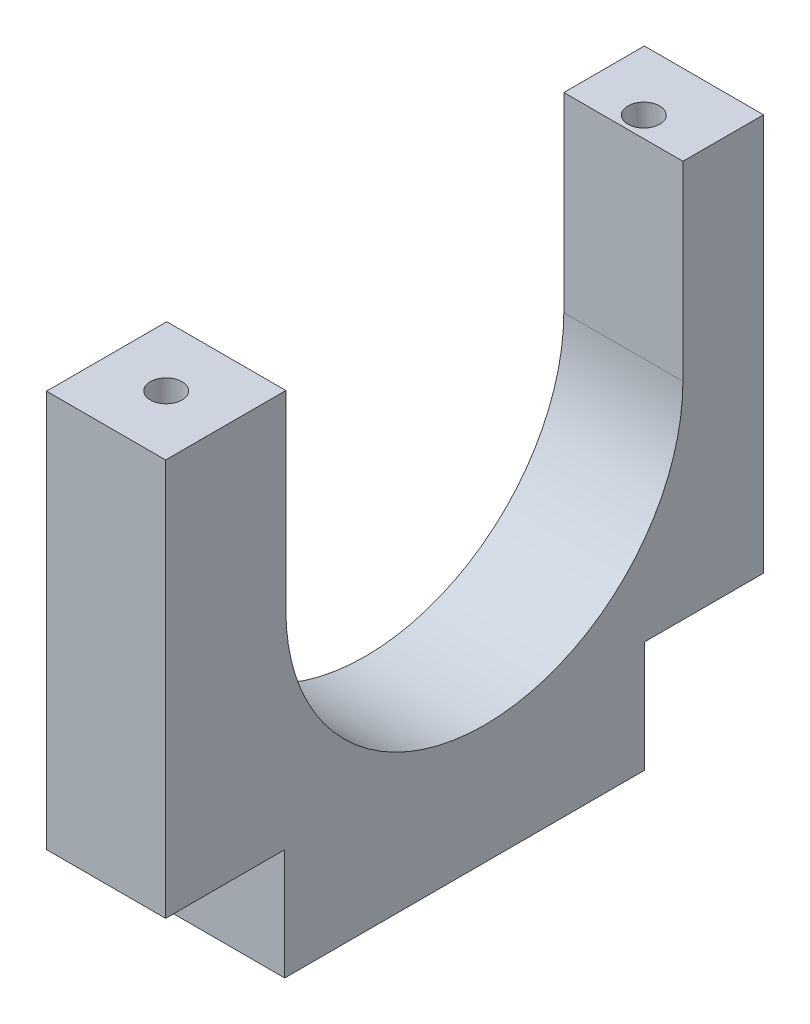
SolidWorks part; units mm, degrees
ref_plane "Front Plane" through (0, 0, 0) normal (0, 0, 1) x (1, 0, 0)
ref_plane "Top Plane" through (0, 0, 0) normal (0, 1, 0) x (1, 0, 0)
ref_plane "Right Plane" through (0, 0, 0) normal (1, 0, 0) x (0, 0, -1)
sketch "Sketch1" plane through (0, 0, 0) normal (0, 1, 0) x (1, 0, 0)
  line L0 (-58, -56) -> (58, -56)
  line L1 (-58, -56) -> (-58, 56)
  line L2 (58, -56) -> (58, 56)
  line L3 (-58, 56) -> (58, 56)
  line L4 (-58, -56) -> (58, 56) construction
  line L5 (58, -56) -> (-58, 56) construction
  line L6 (-63, -61) -> (-63, 61)
  line L7 (-63, 61) -> (63, 61)
  line L8 (63, -61) -> (63, 61)
  line L9 (-63, -61) -> (63, -61)
  point P1 (0, 0)
  dimension "D1" = 116
  dimension "D2" = 112
  dimension "D3" = 5
extrude "Boss-Extrude1" add sketch "Sketch1" along normal blind 15
fillet "Fillet1" radius 10 1 edges at (58, 7.5, -56)
fillet "Fillet2" radius 10 1 edges at (-58, 7.5, -56)
fillet "Fillet3" radius 10 1 edges at (-58, 7.5, 56)
fillet "Fillet4" radius 10 1 edges at (58, 7.5, 56)
sketch "Sketch4" plane through (0, 15, 0) normal (0, 1, 0) x (1, 0, 0)
  line L0 (-63, 61) -> (-63, 62.625)
  line L1 (-63, 62.625) -> (-61.675, 62.625)
  line L2 (-61.675, 62.625) -> (-61.675, 80.1975)
  line L3 (-61.675, 80.1975) -> (-57.925, 80.1975)
  line L4 (-65.425, 45.0525) -> (-65.425, 80.1975)
  line L5 (-65.425, 45.0525) -> (-57.925, 45.0525)
  line L6 (-65.425, 80.1975) -> (-57.925, 80.1975)
  line L7 (-57.925, 45.0525) -> (-57.925, 80.1975)
  line L8 (-65.425, 45.0525) -> (-57.925, 80.1975) construction
  line L9 (-65.425, 80.1975) -> (-57.925, 45.0525) construction
  dimension "D1" = 1.625
  dimension "D2" = 1.325
  dimension "D3" = 3.75
extrude "Boss-Extrude3" add sketch "Sketch4" along normal blind 49.75 and the other way up to surface contours L6 L4 L5 L7
sketch "Sketch5" plane through (-57.925, 0, 0) normal (1, 0, 0) x (0, 0, -1)
  line L0 (45.0525, 64.75) -> (80.1975, 64.75) construction
  circle A0 centre (62.625, 64.75) radius 12.5
  dimension "D1" = 25
extrude "Cut-Extrude1" cut sketch "Sketch5" against normal through all
ref_plane "Plane1" through (-61.675, 0, 0) normal (1, 0, 0) x (0, 0, -1)
sketch "Sketch6" plane through (-57.925, 0, 0) normal (1, 0, 0) x (0, 0, -1)
  line L0 (45.0525, 64.75) -> (50.125, 64.75)
  line L1 (45.0525, 64.75) -> (45.0525, 57.25)
  line L2 (45.0525, 0) -> (45.0525, 64.75) construction
  line L3 (45.0525, 57.25) -> (52.625, 57.25)
  arc A0 (50.125, 64.75) -> (75.125, 64.75) centre (62.625, 64.75) ccw construction
  arc A1 (52.625, 57.25) -> (50.125, 64.75) centre (62.625, 64.75) cw
  dimension "D1" = 7.5
extrude "Boss-Extrude4" add sketch "Sketch6" along normal blind 5
sketch "Sketch9" plane through (0, 64.75, 0) normal (0, 1, 0) x (1, 0, 0)
  line L0 (-52.925, 47.5887) -> (-55.425, 47.5887)
  line L1 (-52.925, 50.125) -> (-52.925, 45.0525) construction
  circle A0 centre (-55.425, 47.5887) radius 1.25
  dimension "D2" = 2.5
  dimension "D1" = 2.5
extrude "Cut-Extrude3" cut sketch "Sketch9" against normal through all
mirror "Mirror1" about plane through (-61.675, 0, 0) normal (1, 0, 0) of "Cut-Extrude3", "Boss-Extrude4"
ref_plane "Plane2" through (0, 0, -62.625) normal (0, 0, -1) x (-1, 0, 0)
mirror "Mirror2" about plane through (0, 0, -62.625) normal (0, 0, -1) of "Mirror1", "Boss-Extrude4", "Cut-Extrude3"
fillet "Fillet6" radius 17.5 1 edges at (-57.925, 7.5, -61)
fillet "Fillet7" radius 17.5 3 edges at (-52.7994, 15, -66.1256) (-54.6248, 15, -53.4908) (-57.925, 15, -62.8612)
fillet "Fillet8" radius 2 1 edges at (-63, 7.5, -45.0525)
fillet "Fillet9" radius 17.5 2 edges at (-63.5858, 15, -44.4667) (-61.5, 15, -45.0525)
fillet "Fillet10" radius 17.5 2 edges at (-57.925, 0, -79.3488) (-61.675, 0, -80.1975)
mirror "Mirror4" about plane through (0, 0, 0) normal (0, 0, 1) of "Mirror2", "Mirror1", "Cut-Extrude3", "Boss-Extrude4", "Cut-Extrude1", "Boss-Extrude3"
fillet "Fillet11" radius 2 1 edges at (-63, 7.5, 45.0525)
fillet "Fillet12" radius 17.5 2 edges at (-61.5, 15, 45.0525) (-63.5858, 15, 44.4667)
fillet "Fillet13" radius 17.5 1 edges at (-57.925, 7.5, 61)
fillet "Fillet14" radius 17.5 3 edges at (-54.6248, 15, 53.4908) (-57.925, 15, 62.8612) (-52.7994, 15, 66.1256)
fillet "Fillet15" radius 17.5 2 edges at (-57.925, 0, 79.3488) (-61.675, 0, 80.1975)
mirror "Mirror6" about plane through (0, 0, 0) normal (1, 0, 0) of "Mirror4", "Boss-Extrude3", "Boss-Extrude4", "Cut-Extrude3", "Mirror1", "Mirror2"
fillet "Fillet16" radius 2 1 edges at (63, 7.5, 45.0525)
fillet "Fillet17" radius 17.5 2 edges at (61.5, 15, 45.0525) (63.5858, 15, 44.4667)
fillet "Fillet18" radius 2 1 edges at (63, 7.5, -45.0525)
fillet "Fillet19" radius 17.5 2 edges at (61.5, 15, -45.0525) (63.5858, 15, -44.4667)
fillet "Fillet20" radius 17.5 1 edges at (57.925, 7.5, -61)
fillet "Fillet21" radius 17.5 3 edges at (54.6248, 15, -53.4908) (57.925, 15, -62.8612) (52.7994, 15, -66.1256)
fillet "Fillet22" radius 17.5 1 edges at (57.925, 7.5, 61)
fillet "Fillet23" radius 17.5 3 edges at (57.925, 15, 62.8612) (54.6248, 15, 53.4908) (52.7994, 15, 66.1256)
fillet "Fillet24" radius 17.5 2 edges at (57.925, 0, 79.3488) (61.675, 0, 80.1975)
fillet "Fillet25" radius 17.5 2 edges at (57.925, 0, -79.3488) (61.675, 0, -80.1975)
sketch "Sketch11" plane through (0, 0, 0) normal (0, -1, 0) x (-1, 0, 0)
  line L0 (0, 0) -> (0, 45.4)
  line L1 (0, 45.4) -> (-47.5, 45.4)
  line L3 (-8.25, 0) -> (8.25, 0) construction
  line L4 (0, 8.25) -> (0, -8.25) construction
  line L5 (-47.5, 45.4) -> (47.5, -45.4)
  line L6 (47.5, -45.4) -> (41.3679, -51.8158)
  line L7 (41.3679, -51.8158) -> (-58, 43.159)
  line L8 (-58, -45.0525) -> (-58, 45.0525) construction
  line L9 (41.3679, -51.8158) -> (45.5521, -56)
  line L10 (48, -56) -> (-48, -56) construction
  line L11 (47.5, -45.4) -> (53.7756, -39.1244)
  line L12 (-47.5, 45.4) -> (-41.2244, 51.6756)
  line L13 (-41.2244, 51.6756) -> (53.7756, -39.1244)
  line L14 (53.7756, -39.1244) -> (58, -43.1622)
  line L15 (58, 45.0525) -> (58, -45.0525) construction
  line L16 (-41.2244, 51.6756) -> (-45.7489, 56)
  line L17 (-48, 56) -> (48, 56) construction
  circle A0 centre (-47.5, 45.4) radius 5.875
  circle A1 centre (-47.5, 45.4) radius 8.875
  circle A4 centre (-47.5, -45.4) radius 8.875
  circle A5 centre (-47.5, -45.4) radius 5.875
  circle A6 centre (47.5, 45.4) radius 8.875
  circle A7 centre (47.5, 45.4) radius 5.875
  circle A8 centre (47.5, -45.4) radius 8.875
  circle A9 centre (47.5, -45.4) radius 5.875
  arc A10 (-58, 43.159) -> (-45.7489, 56) centre (-47.5646, 45.4677) cw
  arc A11 (45.5521, -56) -> (58, -43.1622) centre (48.4327, -46.3393) ccw
  line M27 (-58, -45.0525) -> (-58, 45.0525)
  line M28 (-58, 45.0525) -> (-57.925, 45.0525)
  line M29 (-57.925, 45.0525) -> (-57.925, 47.2224)
  arc M30 (-57.925, 47.2224) -> (-48, 56) centre (-48, 46) cw
  line M31 (-48, 56) -> (48, 56)
  line M35 (58, 45.0525) -> (58, -45.0525)
  line M36 (58, -45.0525) -> (57.925, -45.0525)
  line M37 (57.925, -45.0525) -> (57.925, -47.2224)
  arc M38 (57.925, -47.2224) -> (48, -56) centre (48, -46) cw
  line M39 (48, -56) -> (-48, -56)
  dimension "D3" = 11.75
  dimension "D4" = 17.75
  dimension "D1" = 45.4
  dimension "D2" = 47.5
extrude "Boss-Extrude5" add sketch "Sketch11" against normal blind 3.5 contours A8 L9 L14 M39 M38 M37 M36 M35 | A9 L6 A8 L11 | A9 L5 A8 L6 | A9 L11 L13 A8 L5 | A8 L5 A1 L7 | A8 L13 L0 L5 | A1 L5 L0 L13 L1 | A1 L1 L13 | L5 A1 L1 A0 | L1 A1 L12 A0 | A1 L5 A0 L12 L16 | A1 L16 L7 M31 M30 M29 M28 M27
mirror "Mirror7" about plane through (0, 0, 0) normal (0, 0, 1) of "Boss-Extrude5"
sketch "Sketch12" plane through (0, 0, 0) normal (0, -1, 0) x (-1, 0, 0)
  line L0 (0, 0) -> (-4, 0)
  line L1 (0, 0) -> (-0.0984, 56)
  line L2 (-45.7489, 56) -> (45.5521, 56) construction
  line L3 (4, -56.5079) -> (-4, -56.5079)
  line L4 (4, -56.5079) -> (4, 56.5079)
  line L5 (-4, -56.5079) -> (-4, 56.5079)
  line L6 (4, 56.5079) -> (-4, 56.5079)
  line L7 (4, -56.5079) -> (-4, 56.5079) construction
  line L8 (-4, -56.5079) -> (4, 56.5079) construction
  line M6 (-45.7489, -56) -> (-0.0016, -12.2753)
  line M7 (-0.0016, -12.2753) -> (41.3679, -51.8158)
  line M9 (45.5521, -56) -> (-45.7489, -56)
  line M13 (41.3679, 51.8158) -> (-0.0016, 12.2753)
  line M14 (-0.0016, 12.2753) -> (-45.7489, 56)
  line M15 (-45.7489, 56) -> (45.5521, 56)
  dimension "D1" = 4
extrude "Boss-Extrude6" add sketch "Sketch12" against normal up to surface (3.5 mm away) contours L4 L1 M13 M15 M14 | L5 L1 M14 M15 | L5 L4 M9 M7 M6 up to face at (47.5, 3.5, -51.275)
sketch "Sketch13" plane through (0, 0, 0) normal (0, -1, 0) x (-1, 0, 0)
  line L0 (0, 0) -> (0, 42.5)
  circle A0 centre (0, 42.5) radius 1.5
  dimension "D2" = 3
  dimension "D1" = 42.5
extrude "Cut-Extrude4" cut sketch "Sketch13" against normal through all
mirror "Mirror8" about plane through (0, 0, 0) normal (0, 0, 1) of "Cut-Extrude4"
ref_plane "Plane3" through (0, 44.75, 0) normal (0, 1, 0) x (1, 0, 0)
sketch "Sketch14" plane through (0, 44.75, 0) normal (0, 1, 0) x (1, 0, 0)
  circle A0 centre (0, 0) radius 158.4202
extrude "Cut-Extrude6" cut sketch "Sketch14" against normal through all
sketch "Sketch15" plane through (0, 57.25, 0) normal (0, -1, 0) x (-1, 0, 0)
  line L1 (65.425, -45.0525) -> (70.425, -45.0525)
  line L2 (65.425, -45.0525) -> (65.425, -80.1975)
  line L3 (65.425, -80.1975) -> (70.425, -80.1975)
  line L4 (70.425, -45.0525) -> (70.425, -80.1975)
extrude "Cut-Extrude7" cut sketch "Sketch15" against normal through all
mirror "Mirror9" about plane through (-61.675, 0, 0) normal (1, 0, 0) of "Cut-Extrude7"
sketch "Sketch16" plane through (0, 64.75, 0) normal (0, 1, 0) x (1, 0, 0)
  line L1 (-57.925, -80.1975) -> (-65.425, -80.1975)
  line L2 (-57.925, -80.1975) -> (-57.925, -75.125)
  line L3 (-57.925, -75.125) -> (-65.425, -75.125)
  line L4 (-65.425, -80.1975) -> (-65.425, -75.125)
  line L5 (-57.925, -50.125) -> (-65.425, -50.125)
  line L6 (-57.925, -50.125) -> (-57.925, -45.0525)
  line L7 (-57.925, -45.0525) -> (-65.425, -45.0525)
  line L8 (-65.425, -50.125) -> (-65.425, -45.0525)
extrude "Boss-Extrude7" add sketch "Sketch16" along normal blind 12
sketch "Sketch17" plane through (0, 44.75, 0) normal (0, -1, 0) x (-1, 0, 0)
  line L0 (57.925, -80.1975) -> (57.925, -82.6975)
  line L2 (65.425, -80.1975) -> (57.925, -80.1975)
  line L3 (65.425, -80.1975) -> (65.425, -82.6975)
  line L4 (65.425, -82.6975) -> (57.925, -82.6975)
  line L5 (57.925, -80.1975) -> (57.925, -82.6975)
  line M2 (57.925, -80.1975) -> (65.425, -80.1975)
  dimension "D1" = 2.5
extrude "Boss-Extrude8" add sketch "Sketch17" against normal up to surface (32 mm away) contours L4 L3 L0 M2 up to face at (-61.675, 76.75, 77.6613)
ref_plane "Plane4" through (0, 0, 63.875) normal (0, 0, 1) x (1, 0, 0)
mirror "Mirror10" about plane through (0, 0, 63.875) normal (0, 0, 1) of "Boss-Extrude8"
sketch "Sketch18" plane through (0, 44.75, 0) normal (0, -1, 0) x (-1, 0, 0)
  line L0 (61.675, -82.6975) -> (61.675, -78.9125)
  line L1 (65.425, -82.6975) -> (57.925, -82.6975) construction
  circle A0 centre (61.675, -78.9125) radius 1
  dimension "D2" = 2
  dimension "D1" = 3.785
extrude "Cut-Extrude8" cut sketch "Sketch18" against normal through all contours A0
mirror "Mirror11" about plane through (0, 0, 63.875) normal (0, 0, 1) of "Cut-Extrude8"
sketch "Sketch20" plane through (0, 44.75, 0) normal (0, -1, 0) x (-1, 0, 0)
  line L0 (65.425, -82.6975) -> (65.425, -45.0525) construction
  line L1 (57.925, -82.6975) -> (65.425, -82.6975)
  line L2 (57.925, -82.6975) -> (57.925, -75.1975)
  line L3 (57.925, -75.1975) -> (65.425, -75.1975)
  line L4 (65.425, -82.6975) -> (65.425, -75.1975)
  circle A0 centre (61.675, -78.9125) radius 1
  dimension "D1" = 7.5
extrude "Cut-Extrude10" cut sketch "Sketch20" against normal blind 10
sketch "Sketch21" plane through (0, 54.75, 0) normal (0, -1, 0) x (-1, 0, 0)
  line L1 (57.925, -82.6975) -> (65.425, -82.6975)
  line L2 (57.925, -82.6975) -> (57.925, -75.1975)
  line L3 (57.925, -75.1975) -> (65.425, -75.1975)
  line L4 (65.425, -82.6975) -> (65.425, -75.1975)
  circle A0 centre (61.675, -78.9125) radius 2
  dimension "D1" = 4
extrude "Boss-Extrude9" add sketch "Sketch21" along normal blind 3
mirror "Mirror12" about plane through (0, 0, 63.875) normal (0, 0, 1) of "Boss-Extrude9", "Cut-Extrude10", "Cut-Extrude8"
